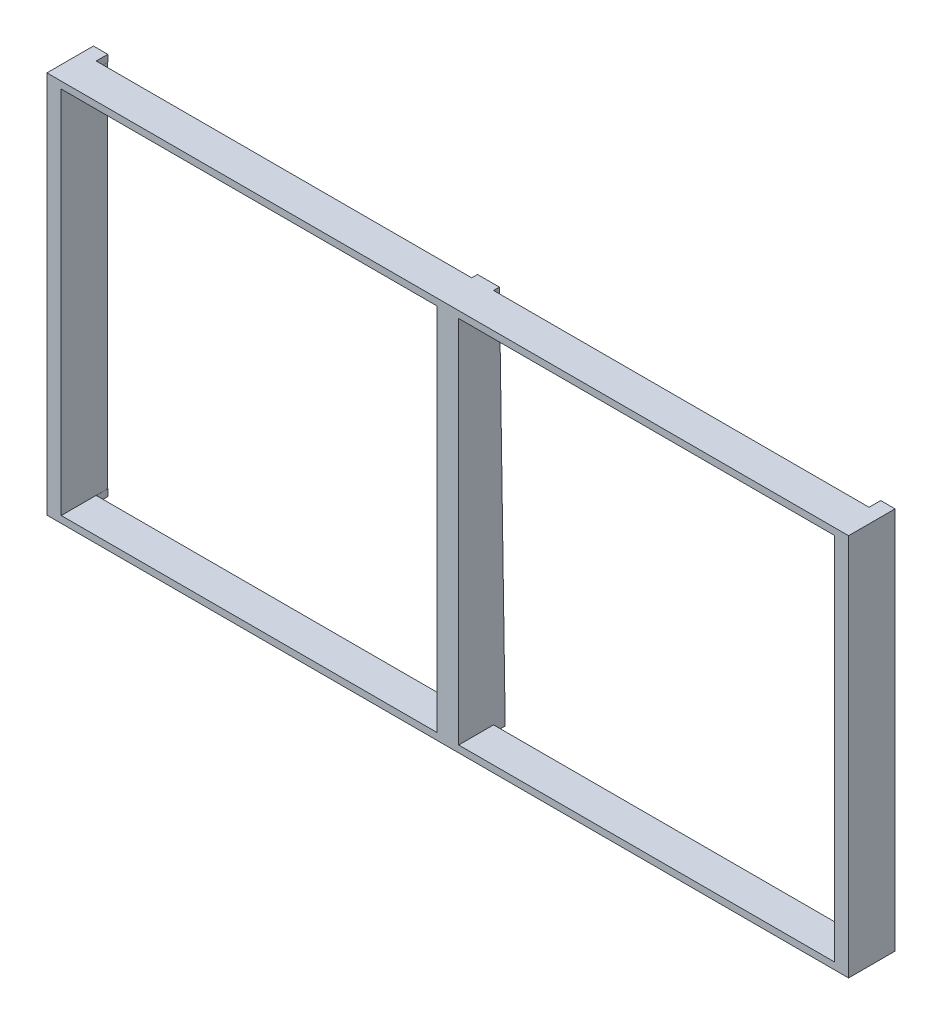
SolidWorks part; units mm, degrees
ref_plane "Спереди" through (0, 0, 0) normal (0, 0, 1) x (1, 0, 0)
ref_plane "Сверху" through (0, 0, 0) normal (0, 1, 0) x (1, 0, 0)
ref_plane "Справа" through (0, 0, 0) normal (1, 0, 0) x (0, 0, -1)
sketch "Эскиз1" plane through (0, 0, 0) normal (0, 0, 1) x (1, 0, 0)
  line L1 (-2930, 1400) -> (2930, 1400)
  line L2 (-2930, 1400) -> (-2930, -1400)
  line L3 (-2930, -1400) -> (2930, -1400)
  line L4 (2930, 1400) -> (2930, -1400)
  line L5 (-2930, 1400) -> (2930, -1400) construction
  line L6 (-2930, -1400) -> (2930, 1400) construction
  line L7 (-2825.3571, 1350) -> (-80, 1350)
  line L8 (-2825.3571, 1350) -> (-2825.3571, -1350)
  line L9 (-2825.3571, -1350) -> (-80, -1350)
  line L10 (-80, 1350) -> (-80, -1350)
  line L11 (80, 1350) -> (2825.3571, 1350)
  line L12 (80, 1350) -> (80, -1350)
  line L13 (80, -1350) -> (2825.3571, -1350)
  line L14 (2825.3571, 1350) -> (2825.3571, -1350)
  point P0 (0, 0)
extrude "Бобышка-Вытянуть1" add sketch "Эскиз1" along normal blind 340
sketch "Эскиз2" plane through (0, -1400, 0) normal (0, -1, 0) x (1, 0, 0)
  line L2 (-2825, 85) -> (-80, 85)
  line L3 (-2825, 85) -> (-2825, 0)
  line L4 (-2825, 0) -> (-80, 0)
  line L5 (-80, 85) -> (-80, 0)
  line L6 (-2825, 85) -> (-80, 0) construction
  line L7 (-2825, 0) -> (-80, 85) construction
  line L8 (0, 424.0898) -> (0, -233.7336) construction
  line L9 (2825, 0) -> (80, 85) construction
  line L10 (2825, 85) -> (80, 0) construction
  line L11 (80, 85) -> (80, 0)
  line L12 (2825, 0) -> (80, 0)
  line L13 (2825, 85) -> (2825, 0)
  line L14 (2825, 85) -> (80, 85)
  line L15 (-2930, 0) -> (2930, 0) construction
  point P2 (-1452.5, 42.5)
  point P15 (1452.5, 42.5)
extrude "Вырез-Вытянуть1" cut sketch "Эскиз2" against normal through all
sketch "Эскиз3" plane through (-80, 0, 0) normal (-1, 0, 0) x (0, 0, 1)
  line L0 (0, 1400) -> (0, -1400)
  line L1 (0, 1400) -> (85, 1400) construction
  line L2 (0, -1400) -> (0, 1400) construction
  line L3 (0, -1400) -> (42.5, 1400)
  line L4 (42.5, 1400) -> (0, 1400)
extrude "Вырез-Вытянуть2" cut sketch "Эскиз3" against normal up to surface (160 mm away) up to face at (80, 0, 127.5)
